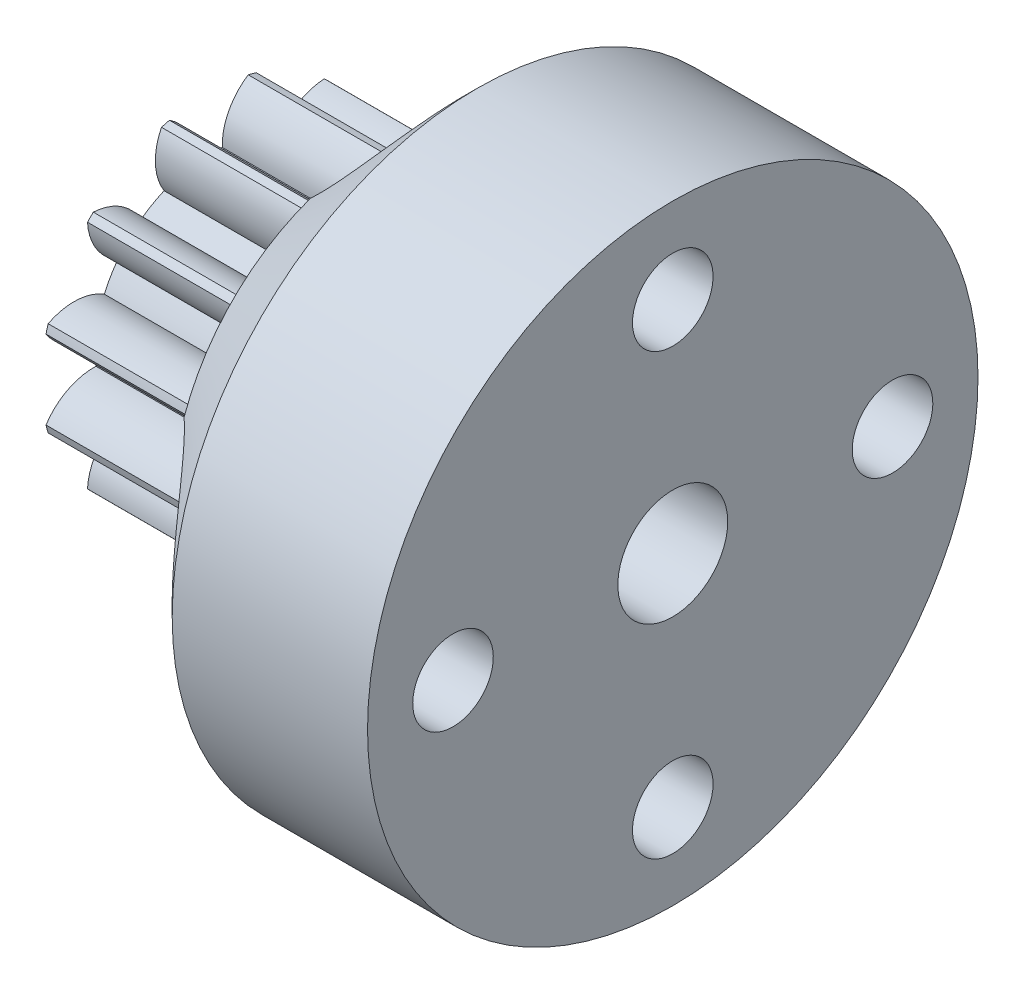
SolidWorks part; units mm, degrees
ref_plane "Plane1" through (0, 0, 0) normal (0, 0, 1) x (1, 0, 0)
ref_plane "Plane2" through (0, 0, 0) normal (0, 1, 0) x (1, 0, 0)
ref_plane "Plane3" through (0, 0, 0) normal (1, 0, 0) x (0, 0, -1)
other "Configuration Table"
sketch "HoldingSke" plane through (0, 0, 0) normal (0, 1, 0) x (1, 0, 0)
  line L0 (0, 0) -> (0.9981, -0.2122)
  line L1 (-15, 0) -> (100, 0) construction
  line L2 (0, 0) -> (-2.1039, 2.3779)
  line L3 (0, 0) -> (-11.863, 4.5341)
  line L4 (0, 0) -> (8.4473, 1.7955)
  line L5 (0, 0) -> (-46.8476, -17.4728)
  line L6 (0, 0) -> (-5.8027, -3.9151)
  line L7 (-2.1039, 2.3779) -> (8.6586, 51.2059)
  line L8 (-76.2, 54.61) -> (-75.5, 54.61)
  line L9 (-71.009, 38.7566) -> (-53.1078, 45.2721)
  line L10 (-76.2, 71.12) -> (104.1128, 71.12)
  line L11 (0, 0) -> (-7, 0)
  line L12 (-76.2, 101.6) -> (-76.162, 101.6)
  line L13 (24.9733, 27.94) -> (52.9518, 28.4284)
  line L14 (24.9733, 27.94) -> (24.9743, 27.94)
  line L15 (24.9733, 27.94) -> (100.4006, 29.5858)
  line L16 (-63.627, -0.98) -> (-12.827, -0.98)
  circle A0 centre (0, 0) radius 1
  circle A1 centre (0, 0) radius 4.654
  circle A2 centre (0, 0) radius 37.5
  circle A3 centre (0, 0) radius 1
  dimension "Num_teeth" = 12
  dimension "Pitch_radius" = 180.3128
  dimension "Width" = 7
  dimension "Thickness" = 7
sketch "BasProSke" plane through (0, 0, 0) normal (0, 1, 0) x (1, 0, 0)
  line L0 (-10, 0) -> (60, 0) construction
  line L1 (0, 0) -> (0, 6.86)
  line L2 (0, 0) -> (7, 0)
  line L3 (7, 0) -> (7, 6.86)
  line L4 (7, 6.86) -> (0, 6.86)
  dimension "Thickness" = 7
  dimension "Diameter" = 13.72
revolve "Base-Revolve" add sketch "BasProSke" angle 360 about L0
sketch "TooCutSke" plane through (0, 0, 0) normal (1, 0, 0) x (0, 0, -1)
  line L1 (0, 0) -> (0, 107) construction
  line L2 (0, 0) -> (-0.8339, 5.8206) construction
  line L3 (0, 0) -> (-3.022, 11.2783) construction
  line L4 (-0.8339, 5.8206) -> (-1.511, 5.6391) construction
  arc A0 (0.552, 4.6211) -> (-0.552, 4.6211) centre (0, 0) ccw
  arc A1 (1.6415, 6.6869) -> (-1.6415, 6.6869) centre (0, 0) ccw
  circle A2 centre (0, 0) radius 5.88 construction
  circle A3 centre (0, 0) radius 5.5254 construction
  arc A4 (-0.552, 4.6211) -> (-1.6415, 6.6869) centre (-2.9026, 4.7016) ccw
  arc A5 (1.6415, 6.6869) -> (0.552, 4.6211) centre (2.9026, 4.7016) ccw
extrude "ToothCut" cut sketch "TooCutSke" along normal through all
fillet "Breaks" [suppressed] radius 0.0196 tangent propagation no
fillet "RootFillets" [suppressed] radius 0.246
pattern_circular "TeethCuts" count 12 every 30 about axis through (-10, 0, 0) along (1, 0, 0) of "ToothCut", "RootFillets", "Breaks"
sketch "HubNeaOneSke" plane through (0, 0, 0) normal (-1, 0, 0) x (0, 0, 1)
  circle A0 centre (0, 0) radius 4.654
  dimension "Diameter" = 9.308
extrude "HubNearOne" [suppressed] add sketch "HubNeaOneSke" along normal blind 43.0001
sketch "HubNeaBotSke" plane through (0, 0, 0) normal (-1, 0, 0) x (0, 0, 1)
  circle A0 centre (0, 0) radius 4.654
  dimension "Diameter" = 9.308
extrude "HubNearBoth" [suppressed] add sketch "HubNeaBotSke" along normal blind 21.5
ref_plane "FarPln" through (7, 0, 0) normal (1, 0, 0) x (0, 0, -1)
sketch "HubFarSke" plane through (7, 0, 0) normal (1, 0, 0) x (0, 0, -1)
  circle A0 centre (0, 0) radius 4.654
  dimension "Diameter" = 9.308
extrude "HubFar" [suppressed] add sketch "HubFarSke" along normal blind 21.5
sketch "BorSke" plane through (0, 0, 0) normal (1, 0, 0) x (0, 0, -1)
  circle A0 centre (0, 0) radius 1
  dimension "Diameter" = 2
extrude "Bore" cut sketch "BorSke" along normal mid plane 100.0001
sketch "KeySke" plane through (0, 0, 0) normal (1, 0, 0) x (0, 0, -1)
  line L0 (-0.8, 0) -> (-0.8, 1.7)
  line L1 (-0.8, 1.7) -> (0.8, 1.7)
  line L2 (0.8, 1.7) -> (0.8, 0)
  line L3 (0, 0) -> (0, 34) construction
  line L4 (-0.8, 0) -> (0.8, 0)
  dimension "Width" = 1.6
extrude "Keyway" [suppressed] cut sketch "KeySke" along normal mid plane 100.0001
pattern_circular "Keyway2" [suppressed] count 2 every 90 about axis through (-10, 0, 0) along (1, 0, 0)
sketch "Sketch1" plane through (7, 0, 0) normal (1, 0, 0) x (0, 0, -1)
  circle A0 centre (0, 0) radius 12.5
  dimension "D1" = 25
extrude "Boss-Extrude1" add sketch "Sketch1" along normal blind 12
sketch "Sketch2" plane through (7, 0, 0) normal (-1, 0, 0) x (0, 0, 1)
  circle A0 centre (0, 9) radius 1.65
  point P2 (0, 0)
  dimension "D1" = 3.3
  dimension "D2" = 9
extrude "Cut-Extrude1" cut sketch "Sketch2" against normal through all
sketch "Sketch3" plane through (7, 0, 0) normal (-1, 0, 0) x (0, 0, 1)
  circle A0 centre (0, 9) radius 3
  dimension "D1" = 6
extrude "Cut-Extrude2" cut sketch "Sketch3" against normal offset from surface (9 mm away) 3 up to face at (19, 9, 1.65)
pattern_circular "CirPattern1" count 4 over 360 about axis through (19, 0, 0) along (-1, 0, 0) of "Cut-Extrude1", "Cut-Extrude2" reverse direction yes
chamfer "Chamfer1" distance 4 angle 45 1 edges at (7, 0, -12.5)
sketch "Sketch4" plane through (19, 0, 0) normal (1, 0, 0) x (0, 0, -1)
  circle A0 centre (0, 0) radius 2.25
  dimension "D1" = 4.5
extrude "Cut-Extrude3" cut sketch "Sketch4" against normal blind 6
equation "' \"Module@HoldingSke\" = 6.35"
equation "' \"Num_teeth@HoldingSke\" = 12"
equation "' \"Ap@HoldingSke\" =  20"
equation "' \"Ap@HoldingSke\" = 20"
equation "' \"Width@HoldingSke\" = 0.5 * 25.4"
equation "' \"Hub_dia@HoldingSke\"= 1 * 25.4"
equation "' \"Hub_dia@HoldingSke\" = 1 * 25.4"
equation "' \"Overall_len@HoldingSke\" = 1.0 * 25.4"
equation "' \"Bore@HoldingSke\" = 0.75 * 25.4"
equation "' \"T_dim@HoldingSke\" = 0.1 * 25.4"
equation "' \"Width@KeySke\" = 0.25 * 25.4"
equation "' \"Show_teeth@HoldingSke\" = 13"
equation "' \"Backlash@HoldingSke\" = 0.009 * 25.4"
equation "' \"Addendum_fac@HoldingSke\" = 1.0"
equation "' \"Dedendum_fac@HoldingSke\" = 1.25"
equation "' \"Dedendum_add@HoldingSke\" = 0.00005 * 25.4"
equation "' \"Clearance_fac@HoldingSke\" = 0.25"
equation "\"Pitch@HoldingSke\" = 1 / \"Module@HoldingSke\""
equation "\"Overcut_dia@TooCutSke\" = (\"Num_teeth@HoldingSke\" + 2 * \"Addendum_fac@HoldingSke\") / \"Pitch@HoldingSke\" + 0.002 * 25.4"
equation "\"Pitch_dia@TooCutSke\" = \"Num_teeth@HoldingSke\" / \"Pitch@HoldingSke\""
equation "\"Base_dia@TooCutSke\" = \"Num_teeth@HoldingSke\" / \"Pitch@HoldingSke\" * cos((\"Ap@HoldingSke\"  * 3.14159265 / 180))"
equation "\"Root_dia@TooCutSke\" = (\"Num_teeth@HoldingSke\" + 2) / \"Pitch@HoldingSke\" - 2 * (\"Addendum_fac@HoldingSke\" + \"Dedendum_fac@HoldingSke\") / \"Pitch@HoldingSke\" - \"Dedendum_add@HoldingSke\" * 2"
equation "\"Half_ang@TooCutSke\" = 180 / \"Num_teeth@HoldingSke\""
equation "\"Half_CT@TooCutSke\" = \"Num_teeth@HoldingSke\" / \"Pitch@HoldingSke\" * sin((3.14159265 / 2 / \"Num_teeth@HoldingSke\")) / 2 - 7 * \"Backlash@HoldingSke\" / 4"
equation "\"Flank_rad@TooCutSke\" = \"Num_teeth@HoldingSke\" / \"Pitch@HoldingSke\" / 5"
equation "\"Radius@RootFillets\" = \"Clearance_fac@HoldingSke\" / \"Pitch@HoldingSke\" + \"Dedendum_add@HoldingSke\""
equation "\"Break_rad@Breaks\" = 0.02 / \"Pitch@HoldingSke\""
equation "\"Thickness@HoldingSke\" = \"Width@HoldingSke\""
equation "\"OAL@HoldingSke\" = \"Thickness@HoldingSke\""
equation "\"MHD@HoldingSke\" = (\"Num_teeth@HoldingSke\" + 2) / \"Pitch@HoldingSke\" - 2 * (\"Addendum_fac@HoldingSke\" + \"Dedendum_fac@HoldingSke\")  / \"Pitch@HoldingSke\" - \"Dedendum_add@HoldingSke\" * 2"
equation "\"MBD@HoldingSke\" = (\"Num_teeth@HoldingSke\" + 2) / \"Pitch@HoldingSke\" - 2 * (\"Addendum_fac@HoldingSke\" + \"Dedendum_fac@HoldingSke\")  / \"Pitch@HoldingSke\" - \"Dedendum_add@HoldingSke\" * 2 - 0.002 * 25.4"
equation "\"MHD@HoldingSke\" = ((sgn( \"MHD@HoldingSke\" - \"Hub_dia@HoldingSke\" )-1)*( \"MHD@HoldingSke\" - \"Hub_dia@HoldingSke\" ))/-2+ \"Hub_dia@HoldingSke\""
equation "\"MBD@HoldingSke\" = ((sgn( \"MBD@HoldingSke\" - \"Bore@HoldingSke\" )-1)*( \"MBD@HoldingSke\" - \"Bore@HoldingSke\" ))/-2+ \"Bore@HoldingSke\""
equation "\"OAL@HoldingSke\" = ((sgn( \"OAL@HoldingSke\" - \"Overall_len@HoldingSke\" )+1)*( \"OAL@HoldingSke\" - \"Overall_len@HoldingSke\" ))/2 + \"Overall_len@HoldingSke\" + 0.000002 * 25.4"
equation "\"Num_teeth@TeethCuts\" = int( \"Show_teeth@HoldingSke\" ) + 1"
equation "\"Num_teeth@TeethCuts\" = ((sgn( \"Num_teeth@TeethCuts\" - \"Num_teeth@HoldingSke\" )-1)*( \"Num_teeth@TeethCuts\" - \"Num_teeth@HoldingSke\" ))/-2+ \"Num_teeth@HoldingSke\""
equation "\"Num_teeth@TeethCuts\" = ((sgn( \"Num_teeth@TeethCuts\" - 2.0)+1)*( \"Num_teeth@TeethCuts\" - 2.0))/2 +2.0"
equation "\"Angle@TeethCuts\" = 360.0 / \"Num_teeth@HoldingSke\""
equation "\"Diameter@BasProSke\" = (\"Num_teeth@HoldingSke\" + 2 * \"Addendum_fac@HoldingSke\") / \"Pitch@HoldingSke\""
equation "\"Thickness@BasProSke\"  = \"Thickness@HoldingSke\""
equation "' \"Fillet_rad@BasProSke\" =  \"Thickness@HoldingSke\" * 0.05"
equation "' \"Fillet_rad@BasProSke\" = \"Thickness@HoldingSke\" * 0.05"
equation "\"MHD@HoldingSke\" = ((sgn( \"MHD@HoldingSke\" - \"Root_dia@TooCutSke\" )-1)*( \"MHD@HoldingSke\" - \"Root_dia@TooCutSke\" ))/-2+ \"Root_dia@TooCutSke\""
equation "\"Diameter@HubNeaOneSke\" = \"MHD@HoldingSke\""
equation "\"Length@HubNearOne\" = \"OAL@HoldingSke\" - \"Thickness@BasProSke\""
equation "\"Diameter@HubNeaBotSke\" = \"MHD@HoldingSke\""
equation "\"Length@HubNearBoth\" = ( \"OAL@HoldingSke\" - \"Thickness@BasProSke\" ) / 2.0"
equation "\"Thickness@FarPln\" = \"Thickness@BasProSke\""
equation "\"Diameter@HubFarSke\" = \"MHD@HoldingSke\""
equation "\"Length@HubFar\" = ( \"OAL@HoldingSke\" - \"Thickness@BasProSke\" ) / 2.0"
equation "\"Diameter@BorSke\" = \"MBD@HoldingSke\""
equation "\"D1@Bore\" = \"OAL@HoldingSke\" * 2.0"
equation "\"D1@Keyway\" = \"OAL@HoldingSke\" * 2.0"
equation "\"Offset@KeySke\" = \"T_dim@HoldingSke\" + \"MBD@HoldingSke\" / 2.0"
